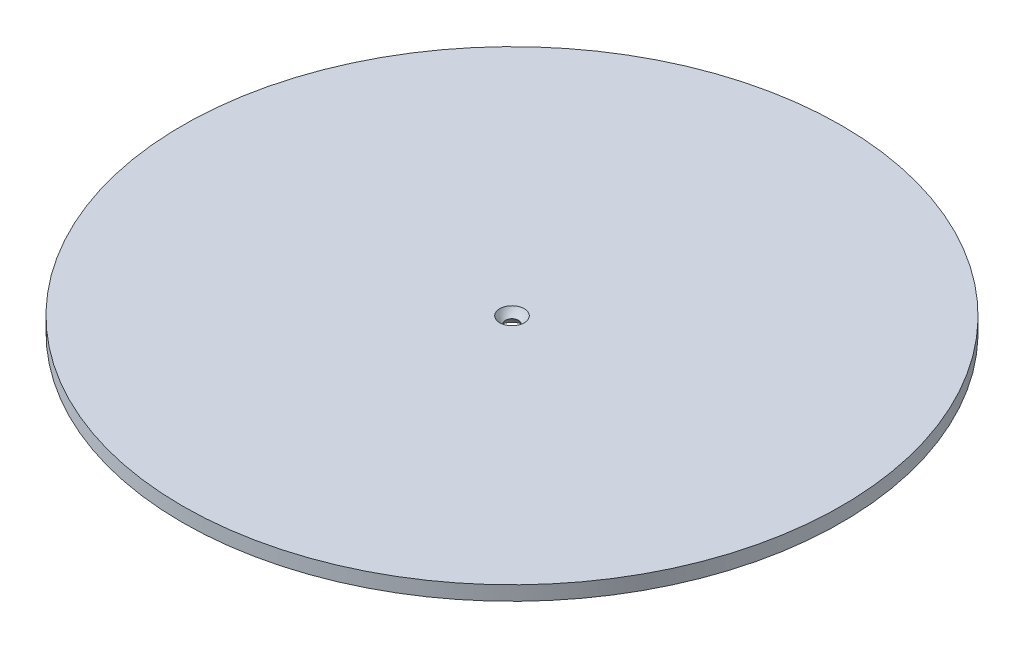
SolidWorks part; units mm, degrees
ref_plane "Front Plane" through (0, 0, 0) normal (0, 0, 1) x (1, 0, 0)
ref_plane "Top Plane" through (0, 0, 0) normal (0, 1, 0) x (1, 0, 0)
ref_plane "Right Plane" through (0, 0, 0) normal (1, 0, 0) x (0, 0, -1)
sketch "Sketch1" plane through (0, 0, 0) normal (0, 1, 0) x (1, 0, 0)
  circle A0 centre (0, 0) radius 1150.0002
  dimension "D1" = 2300.0005
extrude "Boss-Extrude1" add sketch "Sketch1" along normal blind 50
sketch "Sketch2" plane through (0, 0, 0) normal (0, 0, 1) x (1, 0, 0)
  line L0 (0, 0) -> (0, 50)
  line L1 (1150.0002, 50) -> (-1150.0002, 50) construction
  line L2 (0, 50) -> (42.7041, 50)
  line L3 (0, 0) -> (42.7041, 0)
  line L4 (-1150.0002, 0) -> (1150.0002, 0) construction
  arc A0 (42.7041, 0) -> (22.2813, 25.3377) centre (-15.9296, -26.3607) ccw
  arc A1 (22.2813, 25.3377) -> (42.7041, 50) centre (-18.8579, 80.1921) ccw
revolve "Cut-Revolve1" cut sketch "Sketch2" angle 360 about L0
